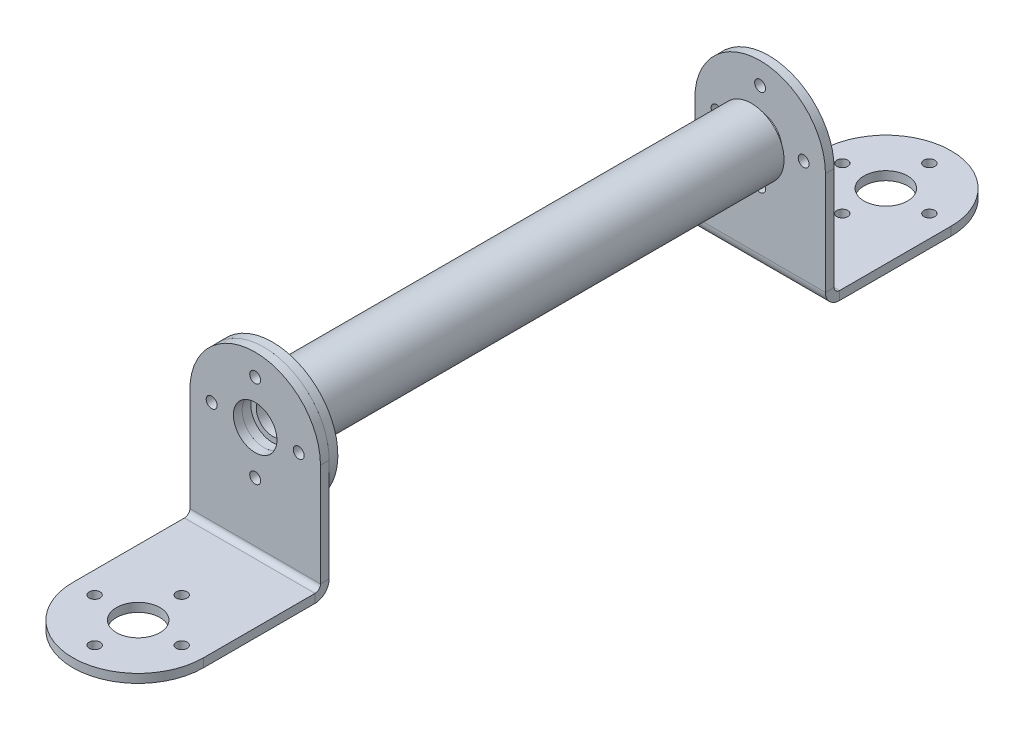
SolidWorks part; units mm, degrees
note: The reader was unsure of these and kept them because the rebuilt part matched: flange length of "Edge-Flange1".
material "1060 Alloy"
ref_plane "Front Plane" through (0, 0, 0) normal (0, 0, 1) x (1, 0, 0)
ref_plane "Top Plane" through (0, 0, 0) normal (0, 1, 0) x (1, 0, 0)
ref_plane "Right Plane" through (0, 0, 0) normal (1, 0, 0) x (0, 0, -1)
sketch "Sketch1" plane through (0, 0, 0) normal (0, 1, 0) x (1, 0, 0)
  line L0 (-12, 0) -> (-12, 21.5)
  line L1 (-12, 21.5) -> (12, 21.5)
  line L2 (12, 21.5) -> (12, 0)
  line L3 (0, 0) -> (8, 0) construction
  line L4 (0, 8) -> (0, 0) construction
  arc A0 (-12, 0) -> (12, 0) centre (0, 0) ccw
  circle A1 centre (0, 0) radius 4
  circle A2 centre (8, 0) radius 1
  circle A3 centre (0, -8) radius 1
  circle A4 centre (-8, 0) radius 1
  circle A5 centre (0, 8) radius 1
  dimension "D1" = 24
  dimension "D2" = 33.5
  dimension "D3" = 8
  dimension "D5" = 3
  dimension "D6" = 2
  dimension "D4" = 4
sheet metal parameters "Sheet-Metal1" thickness 1.6 parameters "D1"=1
sheet metal parameters "Sheet-Metal2" thickness 1.6 parameters "D1"=1
base flange "Base-Flange1" sketch "Sketch1" thickness 1.6 reverse thickness direction no parameters "D1"=1
edge flange "Edge-Flange1" sketch "Sketch7" flange angle 90 flange length 33.5 flange position material outside bend radius 1 thickness 1.6 relief rectangular parameters "D6"=10
sketch "Sketch7" plane through (0, 0, -21.5) normal (0, 0, -1) x (-1, 0, 0)
  line L0 (-12, 0) -> (12, 0) construction
  line L1 (-12, 0) -> (12, 0)
  line L2 (-12, 0) -> (-12, 31.9)
  line L3 (-12, 31.9) -> (12, 31.9)
  line L4 (12, 31.9) -> (12, 0)
bend "EdgeBend1" bend radius 1 bend angle 90 parameters "D5"=1
sketch "Sketch8" plane through (0, 0, -21.5) normal (0, 0, 1) x (1, 0, 0)
  line L0 (-8, 19.9) -> (0, 19.9) construction
  line L1 (-12, 19.9) -> (-12, 31.9)
  line L2 (-12, 31.9) -> (12, 31.9)
  line L3 (12, 31.9) -> (12, 19.9)
  line L4 (0, 19.9) -> (-8, 19.9) construction
  line L5 (0, 19.9) -> (0, 27.9) construction
  circle A0 centre (0, 19.9) radius 4
  circle A1 centre (-8, 19.9) radius 1
  arc A2 (12, 19.9) -> (-12, 19.9) centre (0, 19.9) ccw
  circle A3 centre (0, 27.9) radius 1
  circle A4 centre (8, 19.9) radius 1
  circle A5 centre (0, 11.9) radius 1
  line M1 (-12, 31.9) -> (-12, 1)
  line M3 (12, 1) -> (12, 31.9)
  line M4 (12, 31.9) -> (-12, 31.9)
  dimension "D1" = 8
  dimension "D2" = 2
  dimension "D3" = 3
  dimension "D6" = 90
  dimension "D7" = 8
  dimension "D5" = 4
extrude "Cut-Extrude1" cut sketch "Sketch8" against normal up to next contours A2 L2 M1 | A2 M3 M4 | A0 | A1 | A3 | A4 | A5 normal cut yes
sketch "Sketch9" plane through (0, 0, -23.1) normal (0, 0, -1) x (-1, 0, 0)
  circle A0 centre (0, 27.9) radius 1 construction
  circle A1 centre (8, 19.9) radius 1 construction
  circle A2 centre (0, 19.9) radius 4 construction
  circle A3 centre (-8, 19.9) radius 1 construction
  circle A4 centre (0, 11.9) radius 1 construction
  circle A5 centre (0, 27.9) radius 1
  circle A6 centre (8, 19.9) radius 1
  circle A7 centre (0, 19.9) radius 4
  circle A8 centre (-8, 19.9) radius 1
  circle A9 centre (0, 11.9) radius 1
  circle A10 centre (0, 19.9) radius 12
extrude "Boss-Extrude1" add sketch "Sketch9" along normal blind 1.6 separate body
sketch "Sketch10" plane through (0, 0, -24.7) normal (0, 0, -1) x (-1, 0, 0)
  circle A0 centre (0, 19.9) radius 6
  circle A1 centre (0, 19.9) radius 3
  dimension "D1" = 12
  dimension "D2" = 6
extrude "Boss-Extrude2" add sketch "Sketch10" along normal blind 88
ref_plane "Plane1" through (0, 0, -68.7) normal (0, 0, -1) x (-1, 0, 0)
mirror "Mirror1" about plane through (0, 0, -68.7) normal (0, 0, -1) of bodies 103
bend "DerivedBend1" bend radius 1 bend angle 90 parameters "D5"=1
flat pattern "Flat-Pattern1" [suppressed]
sketch "Bend-Lines1" plane through (0, 0, 0) normal (0, 1, 0) x (-1, 0, 0)
sketch3d "Bounding-Box1" [suppressed]
  line L0 (-12, -21.5, 0) -> (-12, 11.9987, 0) construction
  line L1 (12, -21.5, 0) -> (12, 11.9987, 0) construction
  line L2 (-12, -21.5, 0) -> (12, -21.5, 0) construction
  line L3 (-12, 11.9987, 0) -> (12, 11.9987, 0) construction
bend of the flat pattern "Flatten-<EdgeBend1>1"
flat pattern "Flat-Pattern2" [suppressed]
sketch "Bend-Lines2" plane through (0, 0, 0) normal (0, 1, 0) x (-1, 0, 0)
sketch "Bounding-Box2" [suppressed] plane through (0, 0, 0) normal (0, 1, 0) x (-1, 0, 0)
bend of the flat pattern "Flatten-<DerivedBend1>1"
